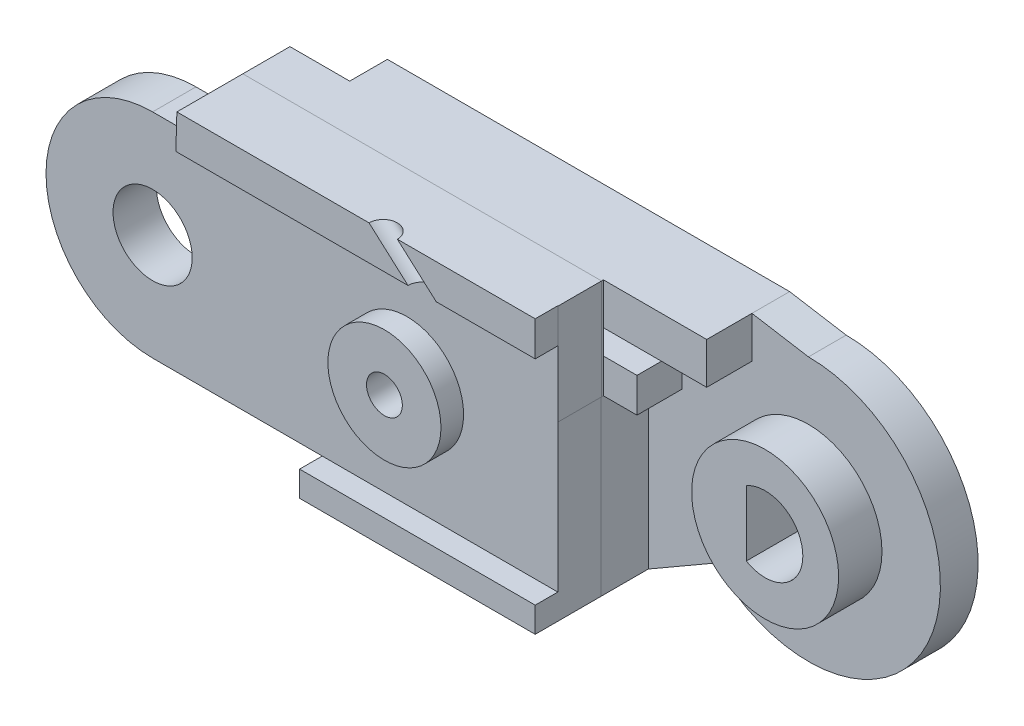
SolidWorks part; units mm, degrees
ref_plane "Front Plane" through (0, 0, 0) normal (0, 0, 1) x (1, 0, 0)
ref_plane "Top Plane" through (0, 0, 0) normal (0, 1, 0) x (1, 0, 0)
ref_plane "Right Plane" through (0, 0, 0) normal (1, 0, 0) x (0, 0, -1)
sketch "Sketch3" plane through (0, 0, 0) normal (0, 0, 1) x (1, 0, 0)
  line L7 (8, 0) -> (9, -2.5)
  line L11 (30, 7) -> (27, 7.5)
  line L13 (0, 7) -> (0, 7.5) construction
  line L14 (0, 7.5) -> (-22.3287, 7.5) construction
  line L15 (0, 5.3) -> (-14, 5.3) construction
  line L16 (0, 4) -> (-14, 4) construction
  line L17 (-14, 4) -> (-14, 5.3) construction
  line L18 (5.6569, 5.6569) -> (5.6569, 7.5)
  line L19 (5.6569, 7.5) -> (27, 7.5)
  line L20 (21.5, -7) -> (9, -7)
  line L21 (9, -7) -> (9, -2.5)
  line L23 (25.0503, -4.9497) -> (21.5, -7)
  arc A4 (8, 0) -> (5.6569, 5.6569) centre (0, 0) ccw
  arc A5 (25.0503, -4.9497) -> (30, 7) centre (30, 0) ccw
  circle A6 centre (0, 0) radius 7 construction
  circle A7 centre (0, 0) radius 3.9 construction
  circle A8 centre (0, 0) radius 5.3 construction
  circle A9 centre (0, 0) radius 4 construction
  dimension "D10" = 0.5
  dimension "D17" = 14
  dimension "D5" = 135
  dimension "D6" = 12.5
  dimension "D7" = 4.5
  dimension "D8" = 1
  dimension "D9" = 45
  dimension "D11" = 1.8431
  dimension "D12" = 30
  dimension "D14" = 3
extrude "Boss-Extrude1" add sketch "Sketch3" along normal blind 2 contours A5 L11 L19 L18 A4 L7 L21 L20 L23
sketch "Sketch20" plane through (0, 0, 0) normal (0, 0, 1) x (1, 0, 0)
  line L0 (0, 7) -> (0, 7.5) construction
  line L1 (0, 7.5) -> (-19.4737, 7.5) construction
  line L2 (0, 5.3) -> (-14, 5.3) construction
  line L3 (0, 4) -> (-14, 4) construction
  line L4 (-14, 4) -> (-14, 5.3) construction
  line L5 (0, 5.3) -> (17.4849, 5.3) construction
  line L6 (17.4849, 5.3) -> (17.4849, 4) construction
  line L7 (17.4849, 4) -> (0, 4) construction
  line L8 (-2.5, 7.5) -> (-2.5, 2.868) construction
  circle A0 centre (0, 0) radius 7 construction
  circle A1 centre (0, 0) radius 3.9 construction
  circle A3 centre (0, 0) radius 5.3 construction
  circle A4 centre (0, 0) radius 4 construction
  circle A5 centre (0, 0) radius 2 construction
  dimension "D1" = 0
  dimension "D2" = 2.5
ref_plane "Plane1" through (0, 0, 2) normal (0, 0, 1) x (1, 0, 0)
sketch "Sketch4" plane through (0, 0, 2) normal (0, 0, 1) x (1, 0, 0)
  line L4 (5.6569, 5.6569) -> (5.6569, 7.5)
  line L5 (5.6569, 5.6569) -> (5.6569, 7.5) construction
  line L6 (5.6569, 7.5) -> (21.5, 7.5)
  line L10 (8, 0) -> (9, -2.5)
  line L11 (9, -2.5) -> (9, -7)
  line L12 (9, -7) -> (21.5, -7)
  line L13 (21.5, -7) -> (21.5, 7.5)
  arc A0 (8, 0) -> (5.6569, 5.6569) centre (0, 0) ccw construction
  arc A3 (8, 0) -> (5.6569, 5.6569) centre (0, 0) ccw
sketch "Sketch22" plane through (0, 0, 2) normal (0, 0, 1) x (1, 0, 0)
  line L0 (5.6569, 5.6569) -> (2.4868, 5.6569)
  line L1 (5.6569, 7.5) -> (21.5, 7.5)
  line L2 (5.6569, 7.5) -> (2.4868, 7.5)
  line L3 (2.4868, 7.5) -> (2.4868, 5.6569)
  line L4 (21.5, 2.172) -> (21.5, 0)
  line L6 (8, 0) -> (9, -2.5)
  line L7 (9, -2.5) -> (9, -7)
  line L8 (9, -7) -> (21.5, -7)
  line L9 (21.5, -7) -> (21.5, 0)
  line L10 (21.5, 7.5) -> (27, 7.5)
  line L11 (27, 7.5) -> (27, 2.172)
  line L12 (27, 2.172) -> (21.5, 2.172)
  arc A0 (8, 0) -> (5.6569, 5.6569) centre (0, 0) ccw
extrude "Boss-Extrude6" add sketch "Sketch22" along normal blind 2.5
sketch "Sketch25" plane through (0, 0, 2) normal (0, 0, 1) x (1, 0, 0)
  line L0 (0, 5.3) -> (18.0981, 5.3) construction
  line L1 (0, 4) -> (18.0981, 4) construction
  line L2 (18.0981, 4) -> (18.0981, 5.3) construction
sketch "Sketch26" plane through (0, 0, 2) normal (0, 0, 1) x (1, 0, 0)
  line L1 (18.0981, 5.3) -> (2.5301, 5.3)
  line L2 (18.0981, 4) -> (2.5301, 4)
  line L3 (2.5301, 5.3) -> (2.5301, 4)
  line L4 (18.0981, 5.3) -> (27, 5.3)
  line L5 (27, 2.172) -> (27, 7.5) construction
  line L6 (27, 5.3) -> (27, 4)
  line L7 (27, 4) -> (18.0981, 4)
extrude "Cut-Extrude6" cut sketch "Sketch26" along normal blind 2.4
sketch "Sketch31" plane through (0, 0, 4.5) normal (0, 0, 1) x (1, 0, 0)
  line L0 (2.4327, 5.6569) -> (0, 5.6569)
  line L4 (9, -5.6569) -> (0, -5.6569)
  line L5 (2.4327, 5.6569) -> (2.4868, 7.5)
  line L6 (2.4868, 7.5) -> (21.5, 7.5)
  line L7 (21.5, -7) -> (21.5, 2.172) construction
  line L8 (27, 7.5) -> (2.4868, 7.5) construction
  line L11 (21.5, -7) -> (9, -7)
  line L12 (9, -7) -> (9, -5.6569)
  line L13 (9, -2.5) -> (9, -7) construction
  line L14 (21.5, 2.172) -> (21.5, -7)
  line L15 (21.5, 7.5) -> (27, 7.5)
  line L16 (27, 7.5) -> (27, 2.172)
  line L17 (27, 2.172) -> (21.5, 2.172)
  arc A0 (0, 5.6569) -> (0, -5.6569) centre (0, 0) ccw
  dimension "D1" = 5.6569
extrude "Boss-Extrude14" add sketch "Sketch31" along normal blind 2.3 separate body
sketch "Sketch32" plane through (0, 0, 6.8) normal (0, 0, 1) x (1, 0, 0)
  circle A0 centre (0, 0) radius 2.1
extrude "Cut-Extrude7" cut sketch "Sketch32" against normal blind 2.3
sketch "Sketch33" plane through (0, 0, 6.8) normal (0, 0, 1) x (1, 0, 0)
  line L0 (2.4868, 7.5) -> (21.5, 7.5)
  line L1 (27, 7.5) -> (2.4868, 7.5) construction
  line L6 (9, -5.6569) -> (21.5, -5.6569)
  line L7 (21.5, -7) -> (21.5, 2.172) construction
  line L8 (21.5, -5.6569) -> (21.5, -7)
  line L9 (21.5, -7) -> (9, -7)
  line L10 (9, -7) -> (9, -5.6569)
  line L12 (2.4868, 7.5) -> (2.4327, 5.6569)
  line L13 (2.4327, 5.6569) -> (21.5, 5.6569)
  line L14 (21.5, 5.6569) -> (21.5, 7.5)
extrude "Boss-Extrude15" add sketch "Sketch33" along normal blind 1.2
sketch "Sketch34" plane through (0, 0, 2) normal (0, 0, 1) x (1, 0, 0)
  line L0 (30, 5.3) -> (18.0981, 5.3) construction
  line L1 (30, 4) -> (18.0981, 4) construction
  circle A0 centre (30, 0) radius 2 construction
  circle A1 centre (30, 0) radius 5.3 construction
  circle A2 centre (30, 0) radius 4 construction
sketch "Sketch35" plane through (0, 0, 6.8) normal (0, 0, 1) x (1, 0, 0)
  line L0 (27, 2.172) -> (27, 7.5)
  line L1 (27, 2.172) -> (21.5204, 2.172)
  line L2 (27, 7.5) -> (21.5204, 7.5)
  line L3 (21.5204, 2.172) -> (21.5204, 7.5)
  line L4 (27, 2.172) -> (27, 7.5) construction
  line L5 (27, 7.5) -> (21.5, 7.5) construction
  dimension "D1" = 0
extrude "Cut-Extrude8" cut sketch "Sketch35" against normal blind 2.4
sketch "Sketch36" plane through (0, 0, 4.4) normal (0, 0, 1) x (1, 0, 0)
  line L0 (27, 2.172) -> (27, 4)
  line L1 (27, 2.172) -> (23.3, 2.172)
  line L2 (27, 4) -> (23.3, 4)
  line L3 (23.3, 2.172) -> (23.3, 4)
  line L4 (21.5, -7) -> (21.5, 7.5) construction
  dimension "D1" = 1.8
extrude "Cut-Extrude9" cut sketch "Sketch36" against normal blind 2.4
sketch "Sketch37" plane through (0, 0, 2) normal (0, 0, 1) x (1, 0, 0)
  circle A0 centre (30, 0) radius 3.9
extrude "Boss-Extrude16" add sketch "Sketch37" along normal blind 2.3
sketch "Sketch39" plane through (0, 0, 4.3) normal (0, 0, 1) x (1, 0, 0)
  line L0 (29, 1.7321) -> (29, -1.7321)
  arc A0 (29, -1.7321) -> (29, 1.7321) centre (30, 0) ccw
  dimension "D2" = 4
  dimension "D1" = 1
extrude "Cut-Extrude10" cut sketch "Sketch39" against normal through all
sketch "Sketch43" plane through (0, 0, 6.8) normal (0, 0, 1) x (1, 0, 0)
  line L0 (21.5, -7) -> (21.5, 7.5) construction
  line L1 (21.5, -5.6569) -> (9, -5.6569) construction
  circle A0 centre (13.5, 0) radius 3
  dimension "D1" = 8
  dimension "D2" = 5.6569
extrude "Boss-Extrude17" add sketch "Sketch43" along normal blind 1.2
sketch "Sketch44" plane through (0, 0, 8) normal (0, 0, 1) x (1, 0, 0)
  circle A0 centre (13.5, 0) radius 0.95
extrude "Cut-Extrude11" cut sketch "Sketch44" against normal through all
sketch "Sketch45" plane through (0, 0, 0) normal (0, 0, -1) x (-1, 0, 0)
  circle A0 centre (-13.5, 0) radius 2
extrude "Cut-Extrude12" cut sketch "Sketch45" against normal blind 3.2
ref_plane "Plane17" through (0, 0, 8) normal (0, 0, 1) x (1, 0, 0)
sketch "Sketch46" plane through (0, 0, 8) normal (0, 0, 1) x (1, 0, 0)
  line L0 (15.5, 5.6569) -> (27.1062, -4.6961) construction
  line L1 (2.4327, 5.6569) -> (21.5, 5.6569) construction
  line L2 (21.5, 5.6569) -> (21.5, 7.5) construction
  dimension "D1" = 6
sketch "Sketch47" plane through (0, 5.6569, 0) normal (0, -1, 0) x (1, 0, 0)
  circle A0 centre (15.5, 8) radius 0.75
extrude "Cut-Extrude13" cut sketch "Sketch47" along direction (0.7462, -0.6657, 0) on the side against the normal blind 5.2
